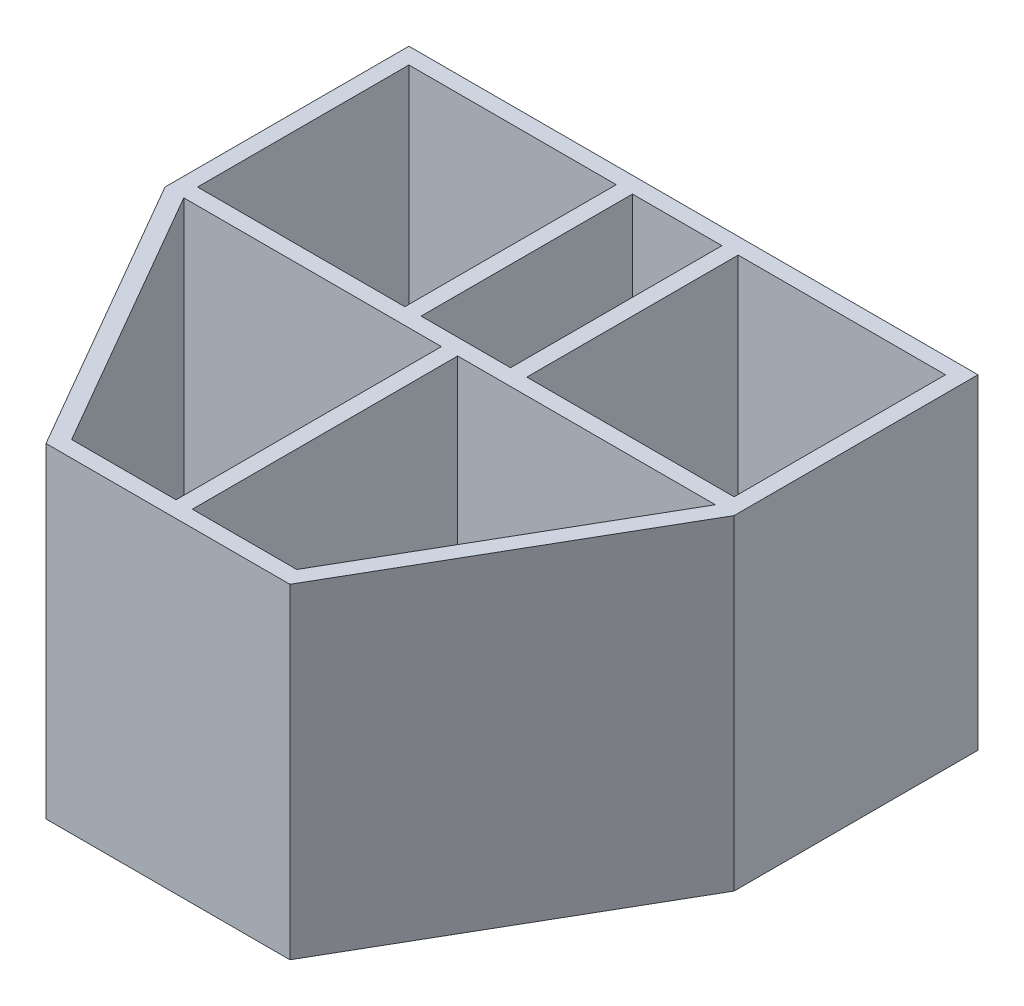
SolidWorks part; units mm, degrees
ref_plane "前视基准面" through (0, 0, 0) normal (0, 0, 1) x (1, 0, 0)
ref_plane "上视基准面" through (0, 0, 0) normal (0, 1, 0) x (1, 0, 0)
ref_plane "右视基准面" through (0, 0, 0) normal (1, 0, 0) x (0, 0, -1)
ref_plane "InnerBottom" through (0, 0, 0) normal (0, 1, 0) x (1, 0, 0)
sketch "Circle" plane through (0, 0, 0) normal (0, 1, 0) x (1, 0, 0)
  line L0 (0, 0) -> (0, 200) construction
  dimension "R" = 200
ref_plane "InnerTop" through (0, 60, 0) normal (0, 1, 0) x (1, 0, 0)
ref_plane "SlotCenterV" through (0, 0, 0) normal (1, 0, 0) x (0, 0, -1)
ref_plane "SlotCenterH" through (0, 0, 0) normal (0, 0, 1) x (1, 0, 0)
ref_axis "CenterAxis" through (0, 0, -200) along (0, 1, 0)
sketch "STwoSlot" [suppressed] plane through (0, 0, 0) normal (0, 1, 0) x (1, 0, 0)
  line L0 (-32.1742, 0) -> (29.2905, 0) construction
  line L1 (0, 21.3687) -> (0, -19.6077) construction
  line L2 (-5, 4) -> (-5, -4)
  line L3 (-5, -4) -> (-7, -4)
  line L4 (-7, -4) -> (-7, -3)
  line L5 (-7, -3) -> (-10, -3)
  line L6 (-10, 3) -> (-7, 3)
  line L7 (-7, 3) -> (-7, 4)
  line L8 (-7, 4) -> (-5, 4)
  line L9 (5, -4) -> (7, -4)
  line L10 (7, -4) -> (7, -3)
  line L11 (7, -3) -> (10, -3)
  line L12 (10, 3) -> (7, 3)
  line L13 (7, 3) -> (7, 4)
  line L14 (7, 4) -> (5, 4)
  line L15 (5, 4) -> (5, -4)
  arc A0 (-10, -3) -> (-10, 3) centre (-10, 0) cw
  arc A1 (10, -3) -> (10, 3) centre (10, 0) ccw
  dimension "D4" = 3
  dimension "D1" = 8
  dimension "D2" = 2
  dimension "D3" = 3
  dimension "D5" = 10
sketch "STwoBase" [suppressed] plane through (0, 0, 0) normal (0, 1, 0) x (1, 0, 0)
  line L0 (0, 7.5) -> (0, -6.5) construction
  line L1 (-17.5, -7.5) -> (17.5, -7.5)
  line L2 (-17.5, -7.5) -> (-17.5, 7.5)
  line L3 (-17.5, 7.5) -> (17.5, 7.5)
  line L4 (17.5, -7.5) -> (17.5, 7.5)
  line L5 (-17.5, -7.5) -> (17.5, 7.5) construction
  line L6 (-17.5, 7.5) -> (17.5, -7.5) construction
  line L7 (-16.5, -6.5) -> (-0.5, -6.5)
  line L8 (-16.5, -6.5) -> (-16.5, 6.5)
  line L9 (-16.5, 6.5) -> (-0.5, 6.5)
  line L10 (16.5, -6.5) -> (16.5, 6.5)
  line L11 (-16.5, -6.5) -> (16.5, 6.5) construction
  line L12 (-16.5, 6.5) -> (16.5, -6.5) construction
  line L13 (-0.5, 6.5) -> (-0.5, -6.5)
  line L14 (0.5, 6.5) -> (0.5, -6.5)
  line L15 (0.5, 6.5) -> (16.5, 6.5)
  line L16 (0.5, -6.5) -> (16.5, -6.5)
  line L17 (0, 6.5) -> (0, -6.5) construction
  point P0 (0, 0)
  point P6 (0, 0)
  dimension "D1" = 35
  dimension "D2" = 15
  dimension "D3" = 1
  dimension "D4" = 1
  dimension "D5" = 1
extrude "FTwoBase" [suppressed] add sketch "STwoBase" along normal blind 20
sketch "SFiveSlotTP1" plane through (0, 0, 0) normal (0, 1, 0) x (1, 0, 0)
  line L0 (0, 21.9383) -> (0, -21.3523) construction
  line L1 (-37.6162, 0) -> (47.1378, 0) construction
  line L2 (-5.15, 11) -> (-5.15, 3)
  line L3 (-5.15, 3) -> (-7.55, 3)
  line L4 (-7.55, 3) -> (-7.55, 4)
  line L5 (-7.55, 4) -> (-10.55, 4)
  line L6 (-10.55, 10) -> (-7.55, 10)
  line L7 (-7.55, 10) -> (-7.55, 11)
  line L8 (-7.55, 11) -> (-5.15, 11)
  line L9 (-10.55, 7) -> (-5.15, 7) construction
  line L10 (7.55, 10) -> (7.55, 11)
  line L11 (10.55, 10) -> (7.55, 10)
  line L12 (7.55, 4) -> (10.55, 4)
  line L13 (7.55, 3) -> (7.55, 4)
  line L14 (5.15, 3) -> (7.55, 3)
  line L15 (5.15, 11) -> (5.15, 3)
  line L16 (7.55, 11) -> (5.15, 11)
  line L17 (-1.2, 7) -> (1.2, 7) construction
  line L18 (-1.2, 11.5) -> (1.2, 11.5)
  line L19 (-1.2, 11.5) -> (-1.2, 2.5)
  line L20 (-1.2, 2.5) -> (1.2, 2.5)
  line L21 (1.2, 11.5) -> (1.2, 2.5)
  line L22 (-7.2169, -4.1) -> (-2.7169, -11.8942)
  line L23 (-2.7169, -11.8942) -> (-4.7953, -13.0942)
  line L24 (-4.7953, -13.0942) -> (-9.2953, -5.3)
  line L25 (-9.2953, -5.3) -> (-7.2169, -4.1)
  line L26 (2.7169, -11.8942) -> (4.7953, -13.0942)
  line L27 (7.2169, -4.1) -> (2.7169, -11.8942)
  line L28 (4.7953, -13.0942) -> (9.2953, -5.3)
  line L29 (9.2953, -5.3) -> (7.2169, -4.1)
  line L30 (-8.2561, -4.7) -> (-3.7561, -12.4942) construction
  line L31 (-6.35, 11) -> (-6.35, 3) construction
  line L32 (6.35, 11) -> (6.35, 3) construction
  arc A0 (-10.55, 4) -> (-10.55, 10) centre (-10.55, 7) cw
  arc A1 (10.55, 4) -> (10.55, 10) centre (10.55, 7) ccw
  dimension "D4" = 3
  dimension "D1" = 8
  dimension "T3" = 2.4
  dimension "D3" = 3
  dimension "B1" = 9
  dimension "D7" = 7
  dimension "T1" = 2.4
  dimension "T2" = 2.4
  dimension "B2" = 9
  dimension "D12" = 60
  dimension "A" = 11.1
  dimension "F" = 9.5
  dimension "F2" = 12.7
sketch "SFiveBaseTP1" plane through (0, 0, 0) normal (0, 1, 0) x (1, 0, 0)
  line L0 (0, 29.2892) -> (0, -26.2802) construction
  line L1 (-17.5, 15) -> (17.5, 15)
  line L2 (17.5, 15) -> (17.5, 0)
  line L3 (17.5, 0) -> (7.5, -17.3205)
  line L4 (7.5, -17.3205) -> (-7.5, -17.3205)
  line L5 (-7.5, -17.3205) -> (-17.5, 0)
  line L6 (-17.5, 0) -> (-17.5, 15)
  line L8 (-16.3453, 0) -> (-6.9226, -16.3205)
  line L9 (-16.5, 14) -> (-3.75, 14)
  line L10 (-16.5, 14) -> (-16.5, 1)
  line L11 (-16.5, 1) -> (-3.75, 1)
  line L12 (16.5, 14) -> (16.5, 1)
  line L13 (-6.9226, -16.3205) -> (-0.5, -16.3205)
  line L14 (-0.5, -16.3205) -> (-0.5, 0)
  line L15 (-0.5, 0) -> (-16.3453, 0)
  line L16 (0.5, 0) -> (0.5, -16.3205)
  line L17 (0.5, -16.3205) -> (6.9226, -16.3205)
  line L18 (6.9226, -16.3205) -> (16.3453, 0)
  line L19 (16.3453, 0) -> (0.5, 0)
  line L20 (-3.75, 14) -> (-3.75, 1)
  line L21 (-2.75, 14) -> (-2.75, 1)
  line L22 (2.75, 14) -> (2.75, 1)
  line L23 (3.75, 14) -> (3.75, 1)
  line L24 (-2.75, 14) -> (2.75, 14)
  line L25 (3.75, 14) -> (16.5, 14)
  line L26 (-2.75, 1) -> (2.75, 1)
  line L27 (3.75, 1) -> (16.5, 1)
  dimension "D1" = 35
  dimension "D2" = 60
  dimension "D3" = 15
  dimension "D4" = 15
  dimension "D5" = 1
  dimension "D6" = 1
  dimension "D7" = 1
  dimension "D8" = 1
  dimension "D9" = 1
  dimension "D10" = 1
  dimension "D11" = 13
  dimension "D12" = 1
  dimension "D13" = 1
  dimension "D14" = 1
  dimension "D15" = 1
  dimension "D16" = 7.5
extrude "FFiveBaseTP1" add sketch "SFiveBaseTP1" along normal blind 20
sketch "SThreeSlot" [suppressed] plane through (0, 0, 0) normal (0, 1, 0) x (1, 0, 0)
  line L0 (-38.3697, 0) -> (49.7492, 0) construction
  line L1 (0, 31.5127) -> (0, -28.5949) construction
  line L2 (-9.2953, -5.3) -> (-4.7953, -13.0942)
  line L3 (-1.2, 11.5) -> (1.2, 11.5)
  line L4 (-1.2, 11.5) -> (-1.2, 2.5)
  line L5 (-1.2, 2.5) -> (1.2, 2.5)
  line L6 (1.2, 11.5) -> (1.2, 2.5)
  line L7 (-9.2953, -5.3) -> (-7.2169, -4.1)
  line L8 (-4.7953, -13.0942) -> (-2.7169, -11.8942)
  line L9 (-7.2169, -4.1) -> (-2.7169, -11.8942)
  line L10 (2.7169, -11.8942) -> (7.2169, -4.1)
  line L11 (2.7169, -11.8942) -> (4.7953, -13.0942)
  line L12 (7.2169, -4.1) -> (9.2953, -5.3)
  line L13 (4.7953, -13.0942) -> (9.2953, -5.3)
  line L14 (-1.2, 7) -> (1.2, 7) construction
  line L15 (-8.2561, -4.7) -> (-3.7561, -12.4942) construction
  dimension "D1" = 60
  dimension "T1" = 2.4
  dimension "T2" = 2.4
  dimension "D2" = 11.1
  dimension "F" = 9.5
  dimension "B1" = 9
  dimension "B2" = 9
  dimension "D3" = 7
sketch "SThreeBase" [suppressed] plane through (0, 0, 0) normal (0, 1, 0) x (1, 0, 0)
  line L0 (-19.047, 0) -> (-7.5, -20)
  line L1 (-7.5, -20) -> (7.5, -20)
  line L2 (7.5, -20) -> (19.047, 0)
  line L3 (19.047, 0) -> (5, 0)
  line L4 (5, 0) -> (5, 15)
  line L5 (5, 15) -> (-5, 15)
  line L6 (-5, 15) -> (-5, 0)
  line L7 (-19.047, 0) -> (-5, 0)
  line L8 (0, 24.0859) -> (0, -25.4306) construction
  line L9 (0, 31.5127) -> (0, -28.5949) construction
  line L11 (4, 0) -> (4, 14)
  line L12 (4, 14) -> (-4, 14)
  line L13 (-4, 14) -> (-4, 0)
  line L14 (-17.315, -1) -> (-4, -1)
  line L15 (-17.315, -1) -> (-6.9226, -19)
  line L16 (-6.9226, -19) -> (-0.5, -19)
  line L17 (6.9226, -19) -> (17.315, -1)
  line L18 (17.315, -1) -> (4, -1)
  line L19 (-4, -1) -> (-0.5, -1)
  line L20 (-4, 0) -> (4, 0)
  line L21 (-0.5, -1) -> (-0.5, -19)
  line L22 (-4, 14) -> (-4, -1) construction
  line L23 (4, -1) -> (4, 14) construction
  line L24 (0.5, -1) -> (0.5, -19)
  line L25 (0.5, -1) -> (4, -1)
  line L26 (0.5, -19) -> (6.9226, -19)
  line L28 (-6.9226, -19) -> (6.9226, -19) construction
  dimension "D1" = 10
  dimension "D2" = 15
  dimension "D3" = 15
  dimension "D4" = 20
  dimension "D5" = 60
  dimension "D7" = 1
  dimension "D6" = 1
extrude "FThreeBase" [suppressed] add sketch "SThreeBase" along normal blind 20
sketch "SUsbSlot" [suppressed] plane through (0, 0, 0) normal (0, 1, 0) x (1, 0, 0)
  line L0 (0, 4.2432) -> (0, -4.6578) construction
  line L2 (-2.5, -6) -> (2.5, -6)
  line L3 (-2.5, -6) -> (-2.5, 6)
  line L4 (-2.5, 6) -> (2.5, 6)
  line L5 (2.5, -6) -> (2.5, 6)
  line L6 (-2.5, -6) -> (2.5, 6) construction
  line L7 (-2.5, 6) -> (2.5, -6) construction
  point P3 (0, 0)
  dimension "UsbL" = 12
  dimension "UsbKd" = 5
sketch "SUsbBase" [suppressed] plane through (0, 0, 0) normal (0, 1, 0) x (1, 0, 0)
  line L1 (-5, -9) -> (5, -9)
  line L2 (-5, -9) -> (-5, 9)
  line L3 (-5, 9) -> (5, 9)
  line L4 (5, -9) -> (5, 9)
  line L5 (-5, -9) -> (5, 9) construction
  line L6 (-5, 9) -> (5, -9) construction
  line L7 (-4, 8) -> (4, 8)
  line L8 (4, -8) -> (4, 8)
  line L9 (-4, -8) -> (4, -8)
  line L10 (-4, -8) -> (-4, 8)
  dimension "D1" = 10
  dimension "D2" = 18
  dimension "D3" = 1
extrude "FUsbBase" [suppressed] add sketch "SUsbBase" along normal blind 20
equation "\"SlotL\"= 9"
equation "\"SlotKD\"= 2.4"
equation "\"B1@SFiveSlotTP1\"=\"SlotL\""
equation "\"B2@SFiveSlotTP1\"=\"SlotL\""
equation "\"T1@SFiveSlotTP1\"=\"SlotKD\""
equation "\"T3@SFiveSlotTP1\"=\"SlotKD\""
equation "\"T2@SFiveSlotTP1\"=\"SlotKD\""
equation "\"T1@SThreeSlot\"=\"SlotKD\""
equation "\"T2@SThreeSlot\"=\"SlotKD\""
equation "\"B1@SThreeSlot\"=\"SlotL\""
equation "\"B2@SThreeSlot\"=\"SlotL\""
equation "\"BaseTn\"=1"
equation "\"D5@SFiveBaseTP1\"=\"BaseTn\""
equation "\"D6@SFiveBaseTP1\"=\"BaseTn\""
equation "\"D7@SFiveBaseTP1\"=\"BaseTn\""
equation "\"D8@SFiveBaseTP1\"=\"BaseTn\""
equation "\"D9@SFiveBaseTP1\"=\"BaseTn\""
equation "\"D10@SFiveBaseTP1\"=\"BaseTn\""
equation "\"D12@SFiveBaseTP1\"=\"BaseTn\""
equation "\"D13@SFiveBaseTP1\"=\"BaseTn\""
equation "\"D5@STwoBase\"=\"BaseTn\""
equation "\"D3@STwoBase\"=\"BaseTn\""
equation "\"D4@STwoBase\"=\"BaseTn\""
equation "\"BaseH\"= 20"
equation "\"D1@FTwoBase\"=\"BaseH\""
equation "\"D1@FFiveBaseTP1\"=\"BaseH\""
equation "\"D6@SThreeBase\"=\"BaseTn\""
equation "\"D1@FThreeBase\"=\"BaseH\""
equation "\"D7@SThreeBase\"=\"BaseTn\""
equation "\"D3@SUsbBase\"=\"BaseTn\""
equation "\"D1@FUsbBase\"=\"BaseH\""
equation "\"D14@SFiveBaseTP1\"=\"BaseTn\""
equation "\"D15@SFiveBaseTP1\"=\"BaseTn\""
